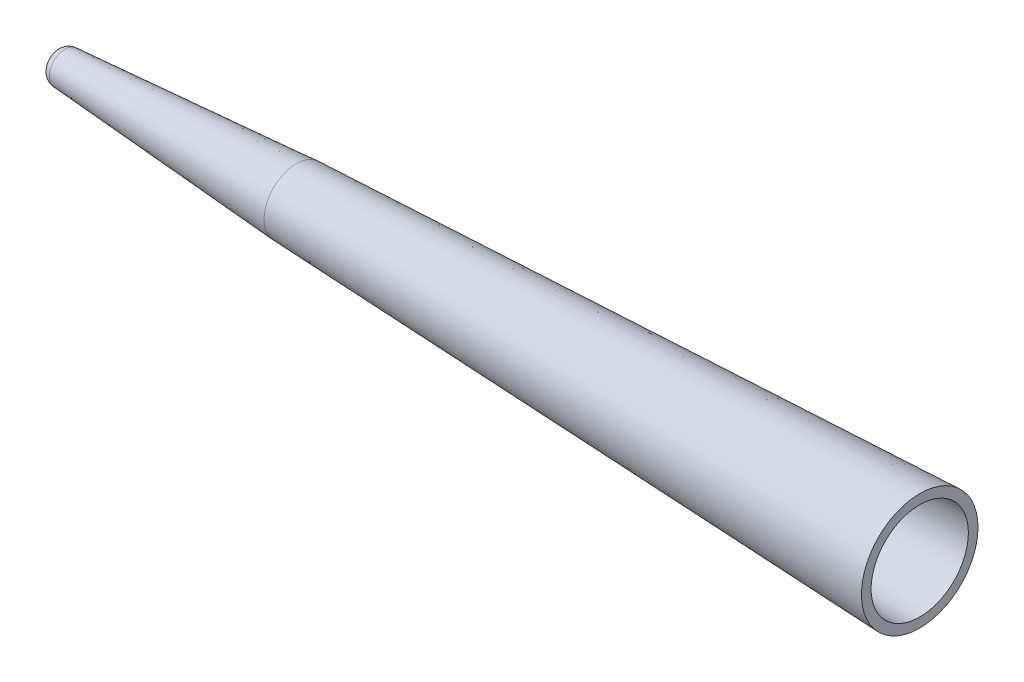
SolidWorks part; units mm, degrees
ref_plane "Front Plane" through (0, 0, 0) normal (0, 0, 1) x (1, 0, 0)
ref_plane "Top Plane" through (0, 0, 0) normal (0, 1, 0) x (1, 0, 0)
ref_plane "Right Plane" through (0, 0, 0) normal (1, 0, 0) x (0, 0, -1)
sketch "Sketch2" plane through (0, 0, 0) normal (0, 0, 1) x (1, 0, 0)
  line L0 (-19.2758, 0) -> (50, 0) construction
  line L1 (0, 21.4747) -> (0, -15.9358) construction
  line L2 (0, 1.2) -> (54.9325, 5.0413) construction
  line L3 (0, 3.2) -> (55.9028, 7.1091) construction
  line L4 (0, 1.2) -> (50, 4.6963)
  line L5 (1.8511, 3.3294) -> (50, 6.6963)
  line L6 (50, 0) -> (50, 20.2328) construction
  line L7 (50, 6.6963) -> (50, 4.6963)
  arc A0 (0, 1.2) -> (1.8511, 3.3294) centre (1.9903, 1.3392) cw
  dimension "D1" = 4
  dimension "D2" = 1.2
  dimension "D3" = 2
  dimension "D4" = 50
revolve "Revolve2" add sketch "Sketch2" angle 360 about L0
ref_plane "Plane1" through (50, 0, 0) normal (1, 0, 0) x (0, 0, -1)
ref_axis "Axis1" through (50, 0, 0) along (-1, 0, 0)
sketch "Sketch3" plane through (0, 0, 0) normal (0, 0, 1) x (1, 0, 0)
  line L0 (50, 6.6963) -> (180, 6.6963) construction
  line L1 (50, -7.366) -> (50, 7.366) construction
  line L2 (50, 6.6963) -> (1.8511, 3.3294) construction
  line L3 (50, 6.6963) -> (180, 12.145) construction
  line L4 (50, 4.6946) -> (180, 10.1432)
  line L5 (180, 10.1432) -> (180, 12.145)
  line L6 (180, 12.145) -> (50, 6.6963)
  line L7 (50, 6.6963) -> (50, 4.6946)
  dimension "D1" = 2.4
  dimension "D2" = 130
  dimension "D3" = 2
revolve "Revolve3" add sketch "Sketch3" angle 360 about axis through (50, 0, 0) along (-1, 0, 0)
ref_plane "Plane2" through (90, 0, 0) normal (1, 0, 0) x (0, 0, -1)
ref_plane "Plane3" through (180, 0, 0) normal (1, 0, 0) x (0, 0, -1)
ref_plane "Plane4" through (0, -12.145, 0) normal (0, 1, 0) x (1, 0, 0)
ref_axis "Axis2" through (180, -12.145, -13.3595) along (0, 0, 1)
ref_plane "Plane5" through (83.9275, 83.9275, 0) normal (-0.7071, -0.7071, 0) x (0, 0, 1)
